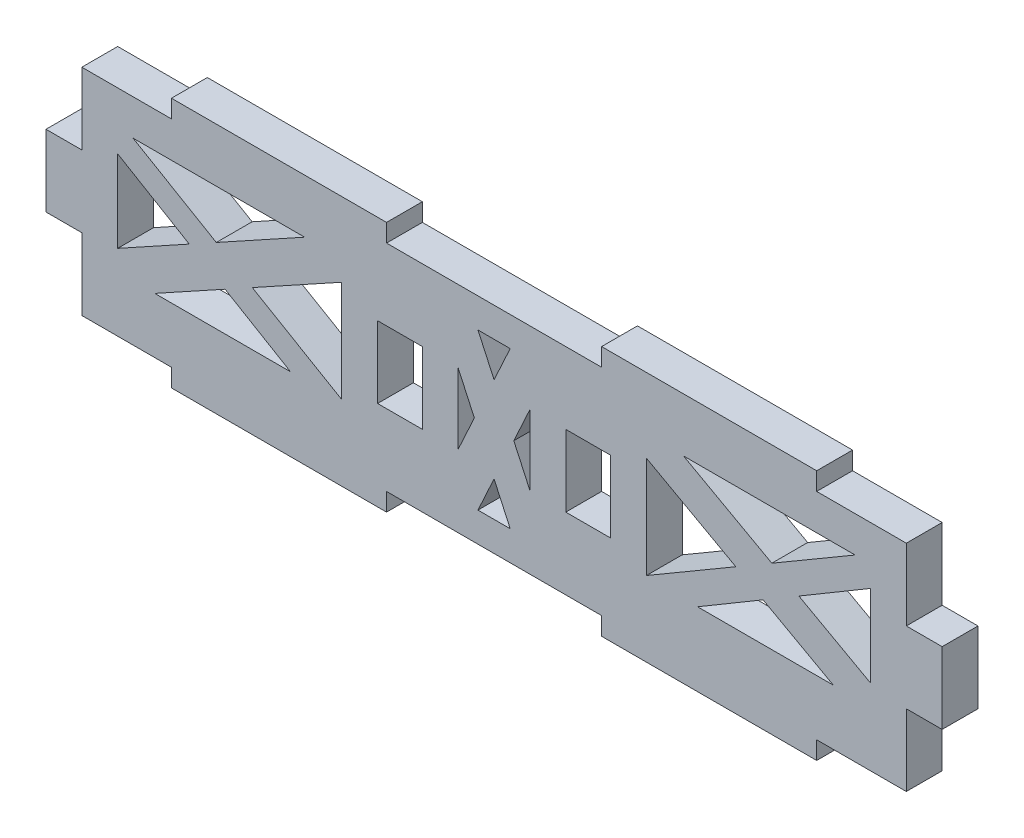
SolidWorks part; units mm, degrees
material "7050-T73510"
ref_plane "Front Plane" through (0, 0, 0) normal (0, 0, 1) x (1, 0, 0)
ref_plane "Top Plane" through (0, 0, 0) normal (0, 1, 0) x (1, 0, 0)
ref_plane "Right Plane" through (0, 0, 0) normal (1, 0, 0) x (0, 0, -1)
sketch "Sketch1" plane through (0, 0, 0) normal (0, 0, 1) x (1, 0, 0)
  line L1 (-158.75, -38.1) -> (158.75, -38.1)
  line L2 (-158.75, -38.1) -> (-158.75, 38.1)
  line L3 (-158.75, 38.1) -> (158.75, 38.1)
  line L4 (158.75, -38.1) -> (158.75, 38.1)
  line L5 (-158.75, -38.1) -> (158.75, 38.1) construction
  line L6 (-158.75, 38.1) -> (158.75, -38.1) construction
  point P0 (0, 0)
  dimension "D1" = 317.5
  dimension "D2" = 76.2
extrude "Boss-Extrude1" add sketch "Sketch1" along normal blind 12.7 contours L1 L3 region at (0, 0, 0)
sketch "Sketch2" plane through (0, 0, 12.7) normal (0, 0, 1) x (1, 0, 0)
  line L0 (-158.75, -38.1) -> (158.75, -38.1) construction
  line L1 (-38.1, -38.1) -> (-114.3, -38.1)
  line L2 (-38.1, -38.1) -> (-38.1, -44.45)
  line L3 (-38.1, -44.45) -> (-114.3, -44.45)
  line L4 (-114.3, -38.1) -> (-114.3, -44.45)
  line L5 (0, -55) -> (0, 55) construction
  line L6 (38.1, -44.45) -> (114.3, -44.45)
  line L7 (114.3, -38.1) -> (114.3, -44.45)
  line L8 (38.1, -38.1) -> (114.3, -38.1)
  line L9 (38.1, -38.1) -> (38.1, -44.45)
  line L10 (55, 0) -> (-55, 0) construction
  line L11 (38.1, 38.1) -> (38.1, 44.45)
  line L12 (38.1, 38.1) -> (114.3, 38.1)
  line L13 (114.3, 38.1) -> (114.3, 44.45)
  line L14 (38.1, 44.45) -> (114.3, 44.45)
  line L15 (-38.1, 44.45) -> (-114.3, 44.45)
  line L16 (-114.3, 38.1) -> (-114.3, 44.45)
  line L17 (-38.1, 38.1) -> (-114.3, 38.1)
  line L18 (-38.1, 38.1) -> (-38.1, 44.45)
  point P12 (-38.1, -41.275)
  dimension "D1" = 76.2
  dimension "D2" = 6.35
  dimension "D3" = 76.2
extrude "Boss-Extrude2" add sketch "Sketch2" against normal blind 12.7
sketch "Sketch3" plane through (0, 0, 12.7) normal (0, 0, 1) x (1, 0, 0)
  line L0 (55, 0) -> (-55, 0) construction
  line L1 (-158.75, -38.1) -> (-146.05, -38.1)
  line L2 (-158.75, -38.1) -> (-158.75, -12.7)
  line L3 (-158.75, -12.7) -> (-146.05, -12.7)
  line L4 (-146.05, -38.1) -> (-146.05, -12.7)
  line L6 (-158.75, 12.7) -> (-146.05, 12.7)
  line L7 (-146.05, 38.1) -> (-146.05, 12.7)
  line L8 (-158.75, 38.1) -> (-146.05, 38.1)
  line L9 (-158.75, 38.1) -> (-158.75, 12.7)
  line L10 (0, -55) -> (0, 55) construction
  line L11 (158.75, 38.1) -> (158.75, 12.7)
  line L12 (158.75, 38.1) -> (146.05, 38.1)
  line L13 (146.05, 38.1) -> (146.05, 12.7)
  line L14 (158.75, 12.7) -> (146.05, 12.7)
  line L15 (158.75, -12.7) -> (146.05, -12.7)
  line L16 (146.05, -38.1) -> (146.05, -12.7)
  line L17 (158.75, -38.1) -> (146.05, -38.1)
  line L18 (158.75, -38.1) -> (158.75, -12.7)
  line L19 (25.4, 12.7) -> (41.275, 12.7)
  line L20 (25.4, 12.7) -> (25.4, -12.7)
  line L21 (25.4, -12.7) -> (41.275, -12.7)
  line L22 (41.275, 12.7) -> (41.275, -12.7)
  line L23 (-38.1, -38.1) -> (38.1, -38.1) construction
  line L24 (-25.4, -12.7) -> (-41.275, -12.7)
  line L25 (-41.275, 12.7) -> (-41.275, -12.7)
  line L26 (-25.4, 12.7) -> (-41.275, 12.7)
  line L27 (-25.4, 12.7) -> (-25.4, -12.7)
  line L28 (-38.1, 38.1) -> (38.1, 38.1) construction
  dimension "D1" = 25.4
  dimension "D2" = 12.7
  dimension "D3" = 50.8
  dimension "D4" = 15.875
  dimension "D5" = 25.4
  dimension "D6" = 25.4
extrude "Cut-Extrude1" cut sketch "Sketch3" against normal through all
sketch "Sketch4" plane through (0, 0, 12.7) normal (0, 0, 1) x (1, 0, 0)
  line L0 (55, 0) -> (-55, 0) construction
  line L1 (-133.35, -18.3931) -> (-53.975, -18.3931)
  line L2 (-133.35, -18.3931) -> (-133.35, 25.4)
  line L3 (-133.35, 25.4) -> (-53.975, 25.4)
  line L4 (-53.975, -18.3931) -> (-53.975, 25.4)
  line L5 (-133.35, -18.3931) -> (-101.6504, -0.9037) construction
  line L6 (0, -55) -> (0, 55) construction
  line L7 (-146.05, 12.7) -> (-146.05, 38.1) construction
  line L8 (-41.275, 12.7) -> (-41.275, -12.7) construction
  line L9 (-146.05, 38.1) -> (-114.3, 38.1) construction
  line L10 (-133.35, 17.8609) -> (-107.9917, 2.85)
  line L11 (-120.2051, -18.3931) -> (-95.3091, -4.6574)
  line L12 (-127.9201, 25.4) -> (-98.411, 8.136)
  line L13 (-133.35, -11.1407) -> (-107.9917, 2.85)
  line L14 (-130.2825, -23.953) -> (-50.9075, 19.8401) construction
  line L15 (-136.4175, -12.8332) -> (-57.0425, 30.9599) construction
  line L16 (100.0125, 0) -> (93.9285, 3.3567) construction
  line L17 (133.35, -18.3931) -> (101.6504, -0.9037) construction
  line L18 (-98.411, 8.136) -> (-67.1199, 25.4)
  line L19 (85.6513, 0.6711) -> (53.975, -17.8609)
  line L20 (-100.0125, 0) -> (-93.9285, 3.3567) construction
  line L21 (-133.35, -18.3931) -> (-53.975, 25.4) construction
  line L22 (-85.6513, 0.6711) -> (-53.975, 18.1476)
  line L23 (-95.3091, -4.6574) -> (-72.1049, -18.3931)
  line L24 (-85.6513, 0.6711) -> (-53.975, -17.8609)
  line L25 (95.3091, -4.6574) -> (72.1049, -18.3931)
  line L26 (85.6513, 0.6711) -> (53.975, 18.1476)
  line L27 (98.411, 8.136) -> (67.1199, 25.4)
  line L28 (133.35, -11.1407) -> (107.9917, 2.85)
  line L29 (127.9201, 25.4) -> (98.411, 8.136)
  line L30 (120.2051, -18.3931) -> (95.3091, -4.6574)
  line L31 (133.35, 17.8609) -> (107.9917, 2.85)
  line L32 (53.975, -18.3931) -> (53.975, 25.4)
  line L33 (133.35, 25.4) -> (53.975, 25.4)
  line L34 (133.35, -18.3931) -> (133.35, 25.4)
  line L35 (133.35, -18.3931) -> (53.975, -18.3931)
  line L36 (-25.4, -12.7) -> (-25.4, 12.7) construction
  line L41 (-12.7, 12.4271) -> (5.7115, -27.6329)
  line L42 (-12.7, -27.6329) -> (12.7, -27.6329)
  line L44 (-12.7, -27.6329) -> (-12.7, 27.6329)
  line L45 (-12.7, 27.6329) -> (12.7, 27.6329)
  line L46 (12.7, -27.6329) -> (12.7, 27.6329)
  line L47 (-12.7, -27.6329) -> (12.7, 27.6329) construction
  line L48 (-12.7, 27.6329) -> (12.7, -27.6329) construction
  line L49 (-5.7115, -27.6329) -> (12.7, 12.4271)
  line L50 (-5.7115, 27.6329) -> (12.7, -12.4271)
  line L51 (-12.7, -12.4271) -> (5.7115, 27.6329)
  line L52 (-6.9302, -30.2847) -> (18.4698, 24.9812) construction
  line L53 (-18.4698, -24.9812) -> (6.9302, 30.2847) construction
  line L54 (-18.4698, 24.9812) -> (6.9302, -30.2847) construction
  line L55 (-6.9302, 30.2847) -> (18.4698, -24.9812) construction
  point P0 (-100.0125, 0)
  point P53 (100.0125, 0)
  point P54 (0, 0)
  dimension "D1" = 12.7
  dimension "D2" = 12.7
  dimension "D3" = 12.7
  dimension "D6" = 12.7
  dimension "D7" = 6.35
  dimension "D4" = 6.35
  dimension "D5" = 6.35
  dimension "D8" = 6.35
extrude "Cut-Extrude2" cut sketch "Sketch4" against normal through all contours L22 L24 L4 | L2 L13 L10 | L12 L18 L3 | L23 L11 L1 | L32 L19 L26 | L35 L30 L25 | L29 L33 L27 | L28 L34 L31 | L45 | L44 | L46 | L42 region at (-95.873, -13.8145, 12.7) region at (-124.8972, 3.1901, 12.7) region at (-64.5338, 0.3193, 12.7) region at (-97.817, 19.6453, 12.7) region at (64.5338, 0.3193, 12.7) region at (95.873, -13.8145, 12.7) region at (97.817, 19.6453, 12.7) region at (124.8972, 3.1901, 12.7) region at (-10.7962, 0, 12.7) region at (0, -23.4906, 12.7) region at (0, 23.4906, 12.7) region at (10.7962, 0, 12.7)
